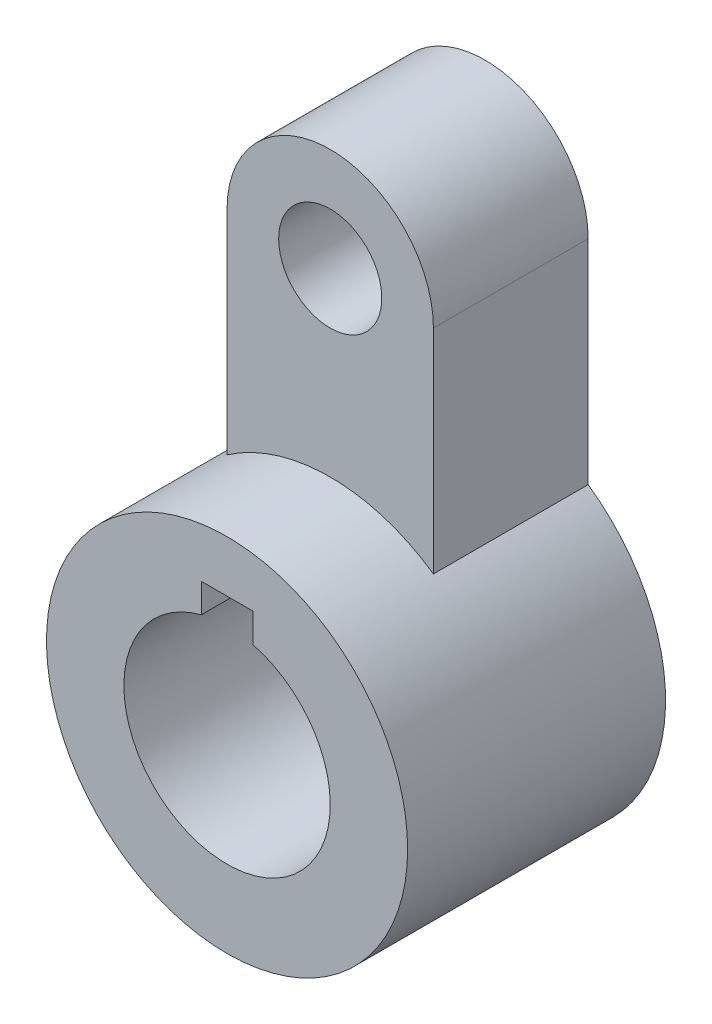
SolidWorks part; units mm, degrees
ref_plane "Front Plane" through (0, 0, 0) normal (0, 0, 1) x (1, 0, 0)
ref_plane "Top Plane" through (0, 0, 0) normal (0, 1, 0) x (1, 0, 0)
ref_plane "Right Plane" through (0, 0, 0) normal (1, 0, 0) x (0, 0, -1)
sketch "Sketch1" plane through (0, 0, 0) normal (0, 0, 1) x (1, 0, 0)
  line L0 (0, -55) -> (0, 55) construction
  line L1 (-12.7, 44.45) -> (-12.7, 18.239)
  line L2 (12.7, 44.45) -> (12.7, 18.239)
  circle A0 centre (0, 0) radius 22.225
  circle A1 centre (0, 44.45) radius 6.35
  arc A2 (12.7, 44.45) -> (-12.7, 44.45) centre (0, 44.45) ccw
  dimension "D2" = 44.45
  dimension "D3" = 12.7
  dimension "D4" = 25.4
  dimension "D1" = 44.45
extrude "Boss-Extrude1" add sketch "Sketch1" along normal blind 31.75 contours A0 region at (0, 0, 0)
extrude "Boss-Extrude2" add sketch "Sketch1<3>" along normal blind 19.05 contours L2 A2 L1 A0 A1 region at (0, 36.6192, 0)
sketch "Sketch1<3>" plane through (0, 0, 0) normal (0, 0, 1) x (1, 0, 0) same geometry as "Sketch1"
sketch "Sketch2" plane through (0, 0, 31.75) normal (0, 0, 1) x (1, 0, 0)
  line L0 (0, -47.625) -> (0, 22.225)
  line L1 (0, 15.875) -> (3.175, 15.875)
  line L2 (3.175, 15.875) -> (3.175, 12.2967)
  line L3 (0, 15.875) -> (-3.175, 15.875)
  line L4 (-3.175, 15.875) -> (-3.175, 12.2967)
  arc A0 (-3.175, 12.2967) -> (3.175, 12.2967) centre (0, 0) ccw
  arc A1 (12.7, 18.239) -> (-12.7, 18.239) centre (0, 0) ccw construction
  point P9 (0, -12.7)
  dimension "D1" = 12.7
  dimension "D2" = 3.175
  dimension "D3" = 3.175
  dimension "D4" = 15.875
extrude "Cut-Extrude1" cut sketch "Sketch2" against normal through all contours L0 A0 L2 L1 | L4 A0 L0 L3 region at (-5.2399, 0.5661, 31.75) region at (5.2399, 0.5661, 31.75)
